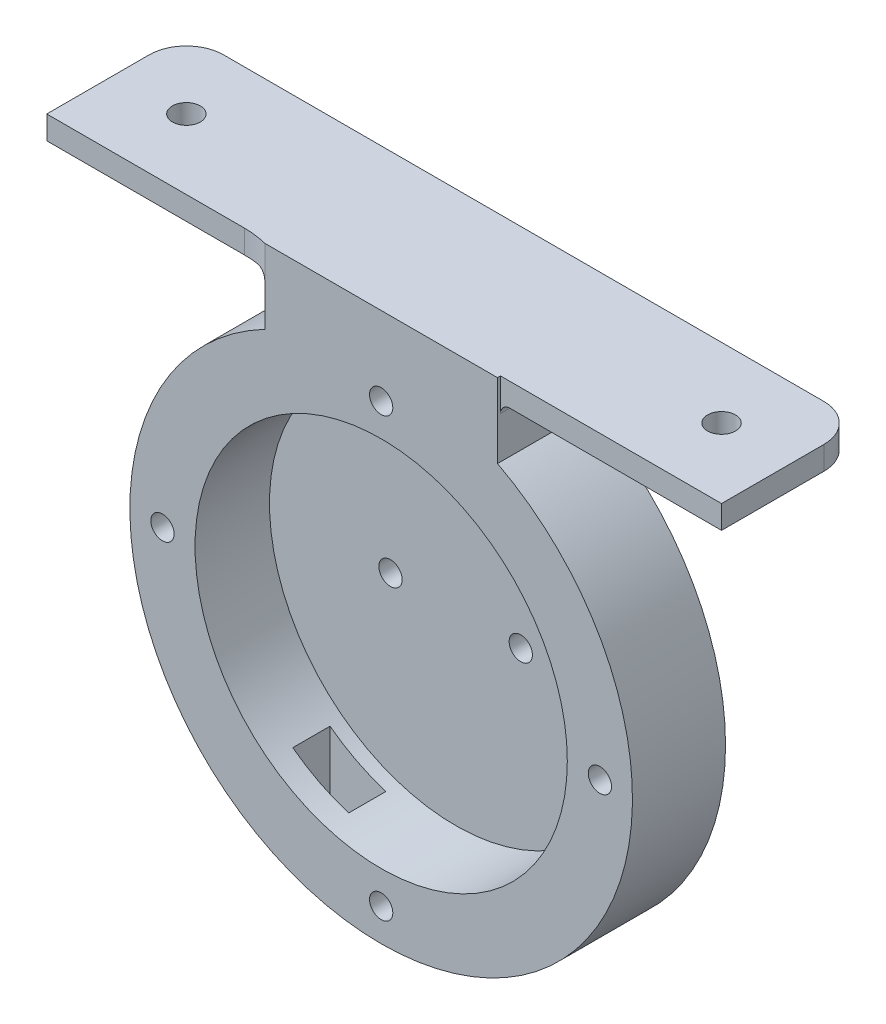
SolidWorks part; units mm, degrees
ref_plane "Front Plane" through (0, 0, 0) normal (0, 0, 1) x (1, 0, 0)
ref_plane "Top Plane" through (0, 0, 0) normal (0, 1, 0) x (1, 0, 0)
ref_plane "Right Plane" through (0, 0, 0) normal (1, 0, 0) x (0, 0, -1)
sketch "Sketch1" plane through (0, 0, 0) normal (0, 0, 1) x (1, 0, 0)
  circle A0 centre (0, 0) radius 27
  circle A1 centre (0, 0) radius 23.5 construction
  circle A2 centre (0, 23.5) radius 1.25
  circle A3 centre (23.5, 0) radius 1.25
  circle A4 centre (0, -23.5) radius 1.25
  circle A5 centre (-23.5, 0) radius 1.25
  circle A6 centre (0, 0) radius 20
  point P15 (0, 0)
  dimension "D1" = 54
  dimension "D2" = 47
  dimension "D3" = 2.5
  dimension "D5" = 40
  dimension "D4" = 4
extrude "Boss-Extrude1" add sketch "Sketch1" along normal blind 10
sketch "Sketch3" plane through (0, 0, 0) normal (0, 0, 1) x (1, 0, 0)
  circle A0 centre (0, 0) radius 20
  circle A1 centre (0, 0) radius 7 construction
  circle A2 centre (-7, 0) radius 1.25
  circle A3 centre (7, 0) radius 1.25
  circle A4 centre (0, 0) radius 11.5 construction
  dimension "D1" = 40
  dimension "D2" = 14
  dimension "D3" = 2.5
  dimension "D4" = 23
extrude "Boss-Extrude2" add sketch "Sketch3" along normal blind 2
sketch "Sketch5" plane through (0, 0, 10) normal (0, 0, 1) x (1, 0, 0)
  line L0 (0, -5.5) -> (0, 5.5) construction
  line L1 (-12.5, 23.9322) -> (-4.2519, 23.9322)
  line L2 (-12.5, 23.9322) -> (-12.5, 31.9322)
  line L3 (-12.5, 31.9322) -> (12.5, 31.9322)
  line L4 (12.5, 23.9322) -> (12.5, 31.9322)
  line L5 (4.2678, 23.9322) -> (0, 26.2545)
  line L6 (0, 26.2545) -> (-4.2519, 23.9322)
  line L7 (4.2678, 23.9322) -> (12.5, 23.9322)
  circle A0 centre (0, 0) radius 27 construction
  dimension "D1" = 12.5
  dimension "D2" = 25
  dimension "D3" = 8
extrude "Boss-Extrude3" add sketch "Sketch5" against normal blind 6
sketch "Sketch4" plane through (0, 0, 0) normal (0, 1, 0) x (1, 0, 0)
  line L0 (27, -10) -> (-27, -10) construction
  line L1 (-12, -3.5) -> (-6, -3.5)
  line L2 (-12, -3.5) -> (-12, -7.5)
  line L3 (-12, -7.5) -> (-6, -7.5)
  line L4 (-6, -3.5) -> (-6, -7.5)
  point P6 (-3, -7.5)
  point P7 (-11.6257, -7.5)
  point P8 (3, -7.5)
  point P9 (-3, -7.5)
  point P11 (-3, -7.5)
  point P12 (3, -3.5)
  point P13 (0, 0)
  point P14 (-3, -3.5)
  dimension "D1" = 4
  dimension "D2" = 6
  dimension "D3" = 2.5
  dimension "D4" = 6
extrude "Cut-Extrude1" cut sketch "Sketch4" against normal up to surface (26.3249 mm away) up to face at (0, 11.9661, 7)
sketch "Sketch6" plane through (0, 31.9322, 0) normal (0, 1, 0) x (1, 0, 0)
  line L0 (12.5, -4) -> (12.5, -10) construction
  line L1 (-12.5, -10) -> (12.5, -10)
  line L2 (-12.5, -10) -> (-12.5, 5.32)
  line L3 (-12.5, 5.32) -> (12.5, 5.32)
  line L4 (12.5, -10) -> (12.5, 5.32)
  point P5 (16.4498, -10)
  dimension "D1" = 15.32
extrude "Boss-Extrude4" add sketch "Sketch6" against normal blind 2.5
sketch "Sketch7" plane through (0, 31.9322, 0) normal (0, 1, 0) x (1, 0, 0)
  line L0 (0, -8.426) -> (0, 8.426) construction
  line L1 (-36.25, -67.18) -> (36.25, -67.18) construction
  line L2 (-36.25, -67.18) -> (-36.25, 1.32) construction
  line L3 (-32.25, 5.32) -> (32.25, 5.32) construction
  line L4 (36.25, -67.18) -> (36.25, 1.32) construction
  line L5 (-28.75, -9.68) -> (-36.25, -9.68)
  line L6 (0, 5.32) -> (-36.25, 5.32)
  line L7 (-36.25, -9.68) -> (-36.25, -2.18)
  line L8 (12.5, -4) -> (-12.5, -4) construction
  line L9 (0, 5.32) -> (0, -9.68)
  line L10 (0, -9.68) -> (-28.75, -9.68)
  line L11 (-36.25, 5.32) -> (-36.25, -2.18)
  arc A0 (32.25, 5.32) -> (36.25, 1.32) centre (32.25, 1.32) cw construction
  arc A1 (-36.25, 1.32) -> (-32.25, 5.32) centre (-32.25, 1.32) cw
  circle A3 centre (-28.75, -2.18) radius 1.5
  point P4 (0, 5.32)
  point P11 (36.25, 5.32)
  point P14 (-36.25, 5.32)
  point P21 (-36.25, -9.68)
  dimension "D4" = 4
  dimension "D7" = 3
  dimension "D1" = 72.5
  dimension "D2" = 72.5
  dimension "D3" = 9.32
  dimension "D5" = 15
extrude "Boss-Extrude5" add sketch "Sketch7" against normal blind 2.5 contours L10 L9 L6 A1 L11 A3 region at (-17.8732, 31.9322, 2.2225)
fillet "Fillet2" radius 10 1 edges at (-12.5, 30.6822, 9.68)
sketch "Sketch8" plane through (0, 31.9322, 0) normal (0, 1, 0) x (1, 0, 0)
  circle A0 centre (-28.75, -2.18) radius 2.5
  circle A1 centre (-28.75, -2.18) radius 4
  dimension "D1" = 5
  dimension "D2" = 8
extrude "Boss-Extrude6" [suppressed] add sketch "Sketch8" against normal blind 5
mirror "Mirror1" about plane through (0, 0, 0) normal (1, 0, 0) of "Boss-Extrude4", "Boss-Extrude5", "Boss-Extrude6"
fillet "Fillet3" radius 1 3 edges at (0, 29.4322, 4) (12.5, 29.4322, 6.84) (-12.5, 29.4322, 7)
fillet "Fillet4" [suppressed] radius 10
